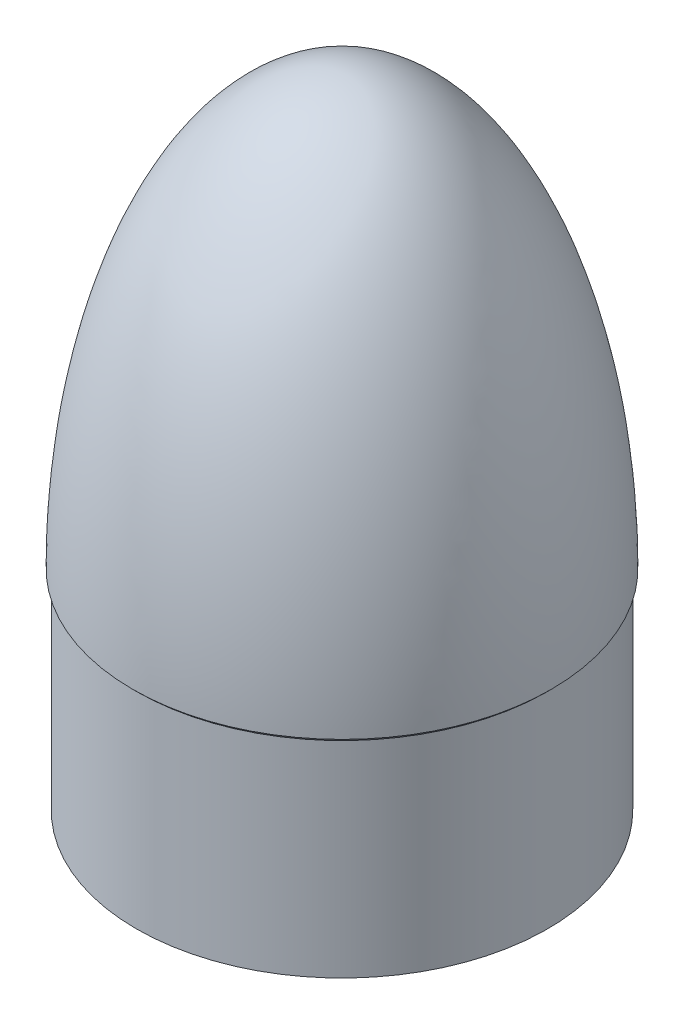
SolidWorks part; units mm, degrees
ref_plane "Front Plane" through (0, 0, 0) normal (0, 0, 1) x (1, 0, 0)
ref_plane "Top Plane" through (0, 0, 0) normal (0, 1, 0) x (1, 0, 0)
ref_plane "Right Plane" through (0, 0, 0) normal (1, 0, 0) x (0, 0, -1)
sketch "Sketch1" plane through (0, 0, 0) normal (0, 0, 1) x (1, 0, 0)
  line L3 (0, 0) -> (0, 202.3003) construction
  line L5 (0, 165.1) -> (0, 163.9)
  line L10 (76.3778, 0) -> (76.3778, -80.772)
  line L12 (76.3778, -80.772) -> (79.375, -80.772)
  line L13 (79.375, -80.772) -> (79.375, -1.397)
  line L14 (80.772, 0) -> (79.375, -1.397)
  line L15 (79.375, -1.397) -> (80.772, -1.397) construction
  line L16 (76.3778, 0) -> (79.557, 3.1792)
  ellipse E0 centre (0, 0) end of major axis (0, 163.9) minor radius 79.572 (79.557, 3.1792) -> (0, 163.9) ccw
  ellipse E1 centre (0, 0) end of major axis (0, -165.1) minor radius 80.772 (80.772, 0) -> (0, 165.1) ccw
  dimension "D1" = 158.75
  dimension "D2" = 79.375
  dimension "D3" = 165.1
  dimension "D4" = 161.544
  dimension "D5" = 2.9972
  dimension "D6" = 1.2
  dimension "D7" = 45
  dimension "D8" = 1.2
  dimension "D9" = 135
revolve "Revolve1" add sketch "Sketch1" angle 360 about L5
